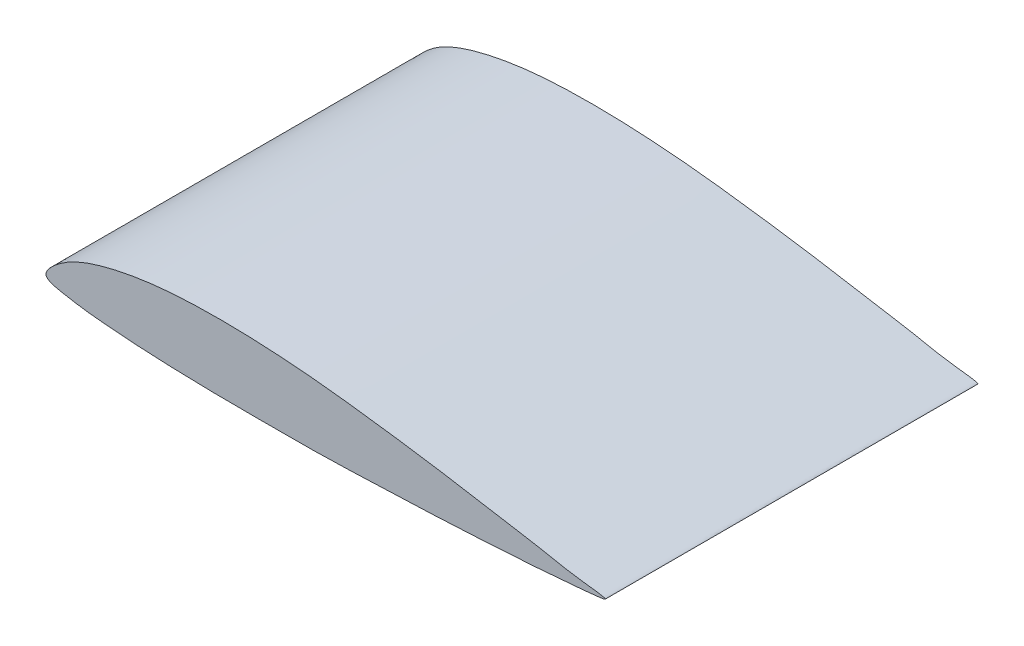
SolidWorks part; units mm, degrees
ref_plane "Спереди" through (0, 0, 0) normal (0, 0, 1) x (1, 0, 0)
ref_plane "Сверху" through (0, 0, 0) normal (0, 1, 0) x (1, 0, 0)
ref_plane "Справа" through (0, 0, 0) normal (1, 0, 0) x (0, 0, -1)
curve "Кривая1"
  spline degree 3 poles (0.9423, 0.0078, 0) (1.0288, -0.0001, 0) (0.9427, -0.0071, 0) (0.8877, -0.0122, 0) (0.7986, -0.0179, 0) (0.7004, -0.0234, 0) (0.5999, -0.027, 0) (0.5001, -0.0313, 0) (0.4, -0.0313, 0) (0.3, -0.0313, 0) (0.2166, -0.0289, 0) (0.15, -0.0253, 0) (0.1082, -0.0219, 0) (0.0751, -0.0189, 0) (0.0494, -0.015, 0) (0.0263, -0.0111, 0) (-0.0153, -0.0012, 0) (0.0238, 0.0331, 0) (0.0485, 0.0472, 0) (0.0748, 0.058, 0) (0.1078, 0.068, 0) (0.1497, 0.0772, 0) (0.2163, 0.0864, 0) (0.3, 0.0897, 0) (0.4001, 0.0869, 0) (0.5003, 0.0786, 0) (0.6, 0.0658, 0) (0.7006, 0.0516, 0) (0.7985, 0.0342, 0) (0.8878, 0.0202, 0) (0.9423, 0.0078, 0) (1.0288, -0.0001, 0) (0.9427, -0.0071, 0) knots -0.099674 -0.049826 -0.024872 0 0.024772 0.049422 0.098654 0.147845 0.197003 0.246151 0.295271 0.344391 0.39353 0.418128 0.442766 0.455107 0.467513 0.47999 0.493309 0.513371 0.527691 0.540973 0.553836 0.579004 0.603803 0.652983 0.702118 0.751398 0.800887 0.850519 0.900326 0.950174 0.975128 1 1.024772 1.049422 1.098654 periodic
sketch "Эскиз1" plane through (0, 0, 0) normal (0, 0, 1) x (1, 0, 0)
  spline S1 degree 3 poles (141.402, -1.0665) (154.3149, -0.0217) (141.3456, 1.1669) (133.1699, 3.0314) (119.7779, 5.1266) (105.09, 7.7427) (90.003, 9.8704) (75.0385, 11.7968) (60.0204, 13.0336) (44.9994, 13.4614) (32.45, 12.9597) (22.4506, 11.5842) (16.176, 10.2054) (11.2144, 8.6931) (7.2713, 7.0822) (3.5769, 4.9713) (-2.2957, -0.1854) (3.9472, -1.6652) (7.4158, -2.2458) (11.2585, -2.8299) (16.2356, -3.2795) (22.497, -3.8014) (32.4917, -4.3417) (44.9985, -4.6879) (59.9983, -4.6955) (75.0096, -4.7001) (89.9849, -4.0438) (105.0637, -3.5142) (119.7884, -2.688) (133.148, -1.8326) (141.402, -1.0665) (154.3149, -0.0217) (141.3456, 1.1669) knots -0.098654 -0.049422 -0.024772 0 0.024872 0.049826 0.099674 0.149481 0.199113 0.248602 0.297882 0.347017 0.396197 0.420996 0.446164 0.459027 0.472309 0.486629 0.506691 0.52001 0.532487 0.544893 0.557234 0.581872 0.60647 0.655609 0.704729 0.753849 0.802997 0.852155 0.901346 0.950578 0.975228 1 1.024872 1.049826 1.099674 only from (150, 0) to (150, 0)
extrude "Бобышка-Вытянуть1" add sketch "Эскиз1" along normal blind 100
